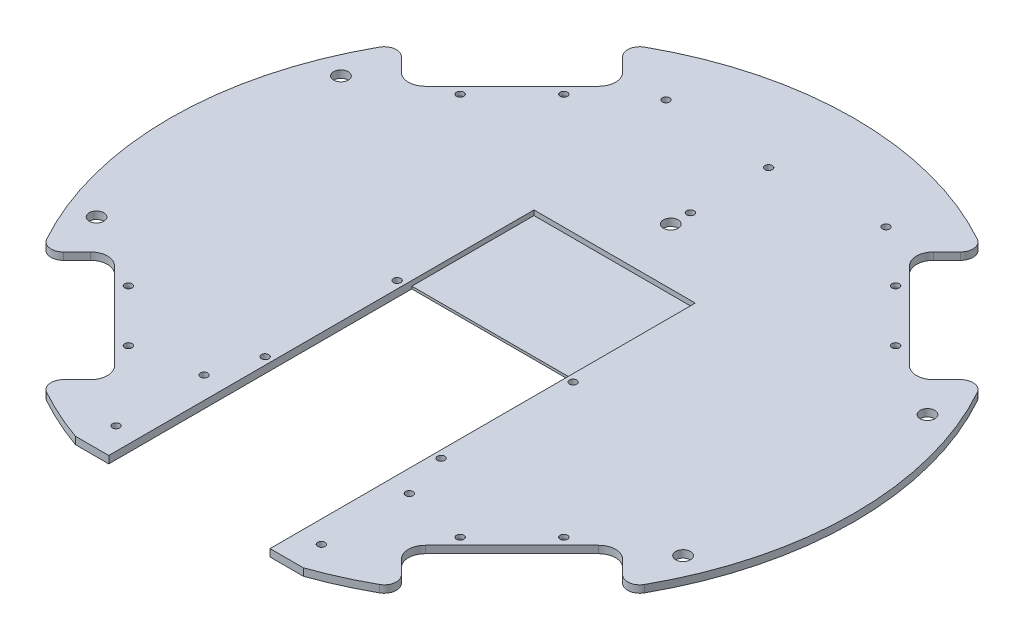
SolidWorks part; units mm, degrees
material "1060 Alloy"
ref_plane "Front Plane" through (0, 0, 0) normal (0, 0, 1) x (1, 0, 0)
ref_plane "Top Plane" through (0, 0, 0) normal (0, 1, 0) x (1, 0, 0)
ref_plane "Right Plane" through (0, 0, 0) normal (1, 0, 0) x (0, 0, -1)
sketch "Sketch1" plane through (0, 0, 0) normal (0, 1, 0) x (1, 0, 0)
  circle A0 centre (0, 0) radius 140
  dimension "D1" = 280
extrude "Boss-Extrude1" add sketch "Sketch1" along normal blind 3
sketch "Sketch7" plane through (0, 3, 0) normal (0, 1, 0) x (1, 0, 0)
  line L0 (-99.0303, -63.6043) -> (-63.6043, -99.0303)
  line L1 (-108.8591, -63.6043) -> (-121.6224, -76.3675)
  line L2 (-63.6043, -108.8591) -> (-76.3675, -121.6224)
  line L3 (-121.6224, -76.3675) -> (-76.3675, -121.6224)
  line L4 (0, 0) -> (-98.9949, -98.9949) construction
  line L7 (0, 0) -> (0, 130) construction
  circle A0 centre (0, 0) radius 140 construction
  arc A1 (-108.8591, -63.6043) -> (-99.0303, -63.6043) centre (-103.9447, -68.5186) cw
  arc A2 (-63.6043, -99.0303) -> (-63.6043, -108.8591) centre (-68.5186, -103.9447) cw
  dimension "D4" = 6.95
  dimension "D1" = 115
  dimension "D2" = 64
  dimension "D3" = 135
extrude "Cut-Extrude4" cut sketch "Sketch7" against normal up to next
sketch "Sketch9" plane through (0, 3, 0) normal (0, 1, 0) x (1, 0, 0)
  line L1 (-63.6043, -99.0303) -> (-99.0303, -63.6043) construction
  line L4 (-108.8591, -63.6043) -> (-119.0017, -73.7469) construction
  circle A0 centre (-89.0955, -67.8823) radius 1.5
  circle A1 centre (-67.8823, -89.0955) radius 1.5
  dimension "D4" = 3
  dimension "D1" = 4
  dimension "D2" = 30
  dimension "D3" = 17
  dimension "D5" = 4
extrude "Cut-Extrude6" cut sketch "Sketch9" against normal up to next
fillet "Fillet1" radius 5 2 edges at (-73.7469, 1.5, 119.0017) (-119.0017, 1.5, 73.7469)
pattern_circular "CirPattern1" count 4 over 360 about axis through (0, 3, 0) along (0, 1, 0) of "Cut-Extrude4", "Fillet1", "Cut-Extrude6"
sketch "Sketch2" plane through (0, 3, 0) normal (0, 1, 0) x (1, 0, 0)
  line L0 (-46.6476, -132) -> (-33, -132)
  line L1 (-33, -132) -> (-33, -8)
  line L2 (-33, -8) -> (33, -8)
  line L3 (33, -8) -> (33, -132)
  line L4 (33, -132) -> (46.6476, -132)
  line L5 (46.6476, -132) -> (46.6476, -140)
  line L6 (46.6476, -140) -> (-46.6476, -140)
  line L7 (-46.6476, -140) -> (-46.6476, -132)
  circle A0 centre (0, 0) radius 140 construction
  dimension "D1" = 8
  dimension "D2" = 124
  dimension "D3" = 66
  dimension "D4" = 13.6476
extrude "Cut-Extrude1" cut sketch "Sketch2" against normal up to next
fillet "Fillet3" radius 1.5 8 edges at (67.8823, 0, 90.5955) (89.0955, 0, 69.3823) (89.0955, 0, -66.3823) (67.8823, 0, -87.5955) (-67.8823, 0, -87.5955) (-89.0955, 0, -66.3823) (-67.8823, 0, 90.5955) (-89.0955, 0, 69.3823)
sketch "Sketch10" plane through (0, 3, 0) normal (0, 1, 0) x (1, 0, 0)
  circle A0 centre (-36, -65) radius 1.5
  circle A1 centre (36, -65) radius 1.5
  circle A2 centre (-36, -11) radius 1.5
  circle A3 centre (36, -11) radius 1.5
  dimension "D3" = 3
  dimension "D1" = 36
  dimension "D2" = 72
  dimension "D4" = 65
  dimension "D5" = 54
extrude "Cut-Extrude7" cut sketch "Sketch10" against normal up to next
sketch "Sketch13" plane through (0, 3, 0) normal (0, 1, 0) x (1, 0, 0)
  line L1 (-33, -132) -> (-46.6476, -132) construction
  circle A0 centre (-42, -84) radius 1.5
  circle A1 centre (-42, -120) radius 1.5
  circle A2 centre (42, -120) radius 1.5
  circle A3 centre (42, -84) radius 1.5
  dimension "D1" = 3
  dimension "D2" = 12
  dimension "D3" = 36
  dimension "D4" = 42
  dimension "D5" = 42
extrude "Cut-Extrude9" cut sketch "Sketch13" against normal up to next
sketch "Sketch16" plane through (0, 3, 0) normal (0, 1, 0) x (1, 0, 0)
  circle A0 centre (0, 73) radius 1.5
  circle A1 centre (-45, 108) radius 1.5
  circle A2 centre (45, 108) radius 1.5
  circle A3 centre (0, 105) radius 1.5
  circle A4 centre (0, 65) radius 3
  dimension "D2" = 3
  dimension "D5" = 6
  dimension "D1" = 73
  dimension "D3" = 108
  dimension "D4" = 90
  dimension "D6" = 32
  dimension "D7" = 65
extrude "Cut-Extrude12" cut sketch "Sketch16" against normal up to next
sketch "Sketch17" plane through (0, 3, 0) normal (0, 1, 0) x (1, 0, 0)
  circle A0 centre (-120, 50) radius 3
  circle A1 centre (-120, -50) radius 3
  circle A2 centre (120, 50) radius 3
  circle A3 centre (120, -50) radius 3
  dimension "D1" = 6
  dimension "D2" = 50
  dimension "D3" = 50
  dimension "D4" = 120
  dimension "D5" = 120
extrude "Cut-Extrude13" cut sketch "Sketch17" against normal up to next
sketch "Sketch18" plane through (0, 3, 0) normal (0, 1, 0) x (1, 0, 0)
  line L1 (-33, -8) -> (33, -8)
  line L2 (-33, -8) -> (-33, 42)
  line L3 (-33, 42) -> (33, 42)
  line L4 (33, -8) -> (33, 42)
  line L6 (33, -8) -> (-33, -8) construction
  line L7 (-33, -8) -> (-33, -132) construction
  dimension "D1" = 50
extrude "Cut-Extrude14" cut sketch "Sketch18" against normal blind 2
